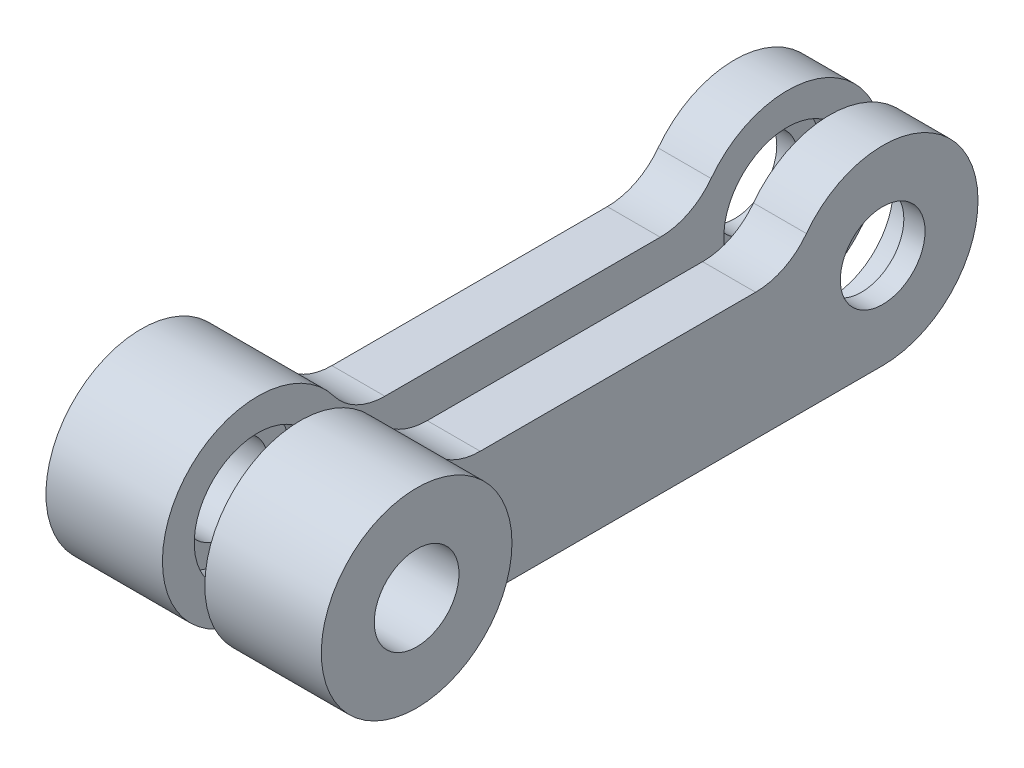
SolidWorks part; units mm, degrees
ref_plane "前视基准面" through (0, 0, 0) normal (0, 0, 1) x (1, 0, 0)
ref_plane "上视基准面" through (0, 0, 0) normal (0, 1, 0) x (1, 0, 0)
ref_plane "右视基准面" through (0, 0, 0) normal (1, 0, 0) x (0, 0, -1)
other "Configuration Table"
sketch "草图1" plane through (0, 0, 0) normal (1, 0, 0) x (0, 0, -1)
  line L1 (0, 0) -> (25, 0)
  line L2 (0, 0) -> (0, -6)
  line L3 (0, -6) -> (25, -6)
  line L4 (25, 0) -> (25, -6)
  circle A0 centre (0, -1.5) radius 4.5
  circle A1 centre (25, -1.5) radius 4.5
  circle A2 centre (0, -1.5) radius 2
  circle A3 centre (25, -1.5) radius 2
  dimension "D1" = 9
  dimension "D2" = 9
  dimension "D4" = 4
  dimension "D3" = 6
  dimension "D5" = 25
extrude "凸台-拉伸1" add sketch "草图1" along normal blind 2.5 contours A0 | L1 L4 L3 L2 | A1
extrude "凸台-拉伸3" add sketch "草图1<5>" against normal blind 3 contours A0
sketch "草图1<5>" plane through (0, 0, 0) normal (1, 0, 0) x (0, 0, -1) same geometry as "草图1"
extrude "切除-拉伸2" cut sketch "草图1<4>" along normal through all both and the other way through all contours L2 A2 | L2 A2 | L4 A3 L1 | L1 A3 L4 region at (0, -1.3854, 0.7577) region at (0, -1.6324, -0.8755) region at (0, -1.3854, -25.7577) region at (0, -1.6324, -24.1245)
sketch "草图1<4>" plane through (0, 0, 0) normal (1, 0, 0) x (0, 0, -1) same geometry as "草图1"
fillet "圆角1" radius 3 2 edges at (1.25, 0, -20.7574) (1.25, 0, -4.2426)
sketch "草图2" plane through (2.5, 0, 0) normal (1, 0, 0) x (0, 0, -1)
  circle A0 centre (0, -1.5) radius 3
  circle A1 centre (25, -1.5) radius 3
  dimension "D1" = 6
extrude "切除-拉伸3" cut sketch "草图2" against normal blind 1.5
ref_plane "基准面1" through (3.5, 0, 0) normal (1, 0, 0) x (0, 0, -1)
mirror "镜向2" about plane through (3.5, 0, 0) normal (1, 0, 0) of bodies 110
